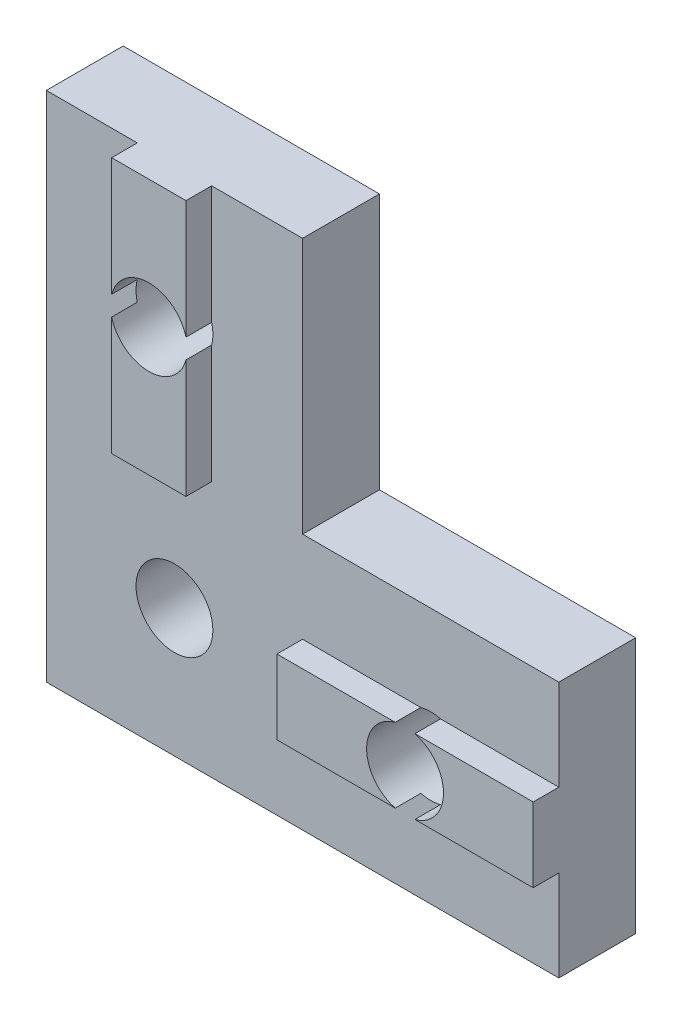
SolidWorks part; units mm, degrees
ref_plane "Front Plane" through (0, 0, 0) normal (0, 0, 1) x (1, 0, 0)
ref_plane "Top Plane" through (0, 0, 0) normal (0, 1, 0) x (1, 0, 0)
ref_plane "Right Plane" through (0, 0, 0) normal (1, 0, 0) x (0, 0, -1)
sketch "Esquisse1" plane through (0, 0, 0) normal (0, 0, 1) x (1, 0, 0)
  line L0 (0, 0) -> (20, 0)
  line L1 (20, 0) -> (20, 10)
  line L2 (20, 10) -> (10, 10)
  line L3 (10, 10) -> (10, 20)
  line L4 (10, 20) -> (0, 20)
  line L5 (0, 20) -> (0, 0)
  point P9 (0, 0)
  point P10 (0, 0)
  point P13 (0, 0)
  point P18 (5, 20)
  point P20 (20, 5)
  dimension "D1" = 10
  dimension "D3" = 20
extrude "Boss.-Extru.1" add sketch "Esquisse1" along normal blind 3
sketch "Esquisse2" plane through (0, 0, 3) normal (0, 0, 1) x (1, 0, 0)
  line L0 (10, 20) -> (0, 20) construction
  line L1 (3.55, 20) -> (6.45, 20)
  line L2 (3.55, 20) -> (3.55, 10)
  line L3 (3.55, 10) -> (6.45, 10)
  line L4 (6.45, 20) -> (6.45, 10)
  line L5 (20, 10) -> (10, 10) construction
  line L6 (20, 0) -> (20, 10) construction
  line L7 (20, 6.45) -> (10, 6.45)
  line L8 (20, 6.45) -> (20, 3.55)
  line L9 (20, 3.55) -> (10, 3.55)
  line L10 (10, 6.45) -> (10, 3.55)
  line L11 (10, 10) -> (10, 20) construction
  point P4 (5, 20)
  point P7 (5, 20)
  point P18 (20, 5)
  point P19 (20, 5)
  dimension "D1" = 2.9
extrude "Boss.-Extru.2" add sketch "Esquisse2" along normal blind 1
sketch "Esquisse4" plane through (0, 0, 4) normal (0, 0, 1) x (1, 0, 0)
  line L0 (10, 20) -> (0, 20) construction
  line L1 (20, 0) -> (20, 10) construction
  circle A0 centre (5, 15) radius 1.5
  circle A1 centre (5, 5) radius 1.5
  circle A2 centre (15, 5) radius 1.5
  point P6 (0, 0)
  point P9 (5, 20)
  point P12 (20, 5)
  dimension "D3" = 3
  dimension "D1" = 5
  dimension "D2" = 5
extrude "Enlèv. mat.-Extru.2" cut sketch "Esquisse4" against normal through all
